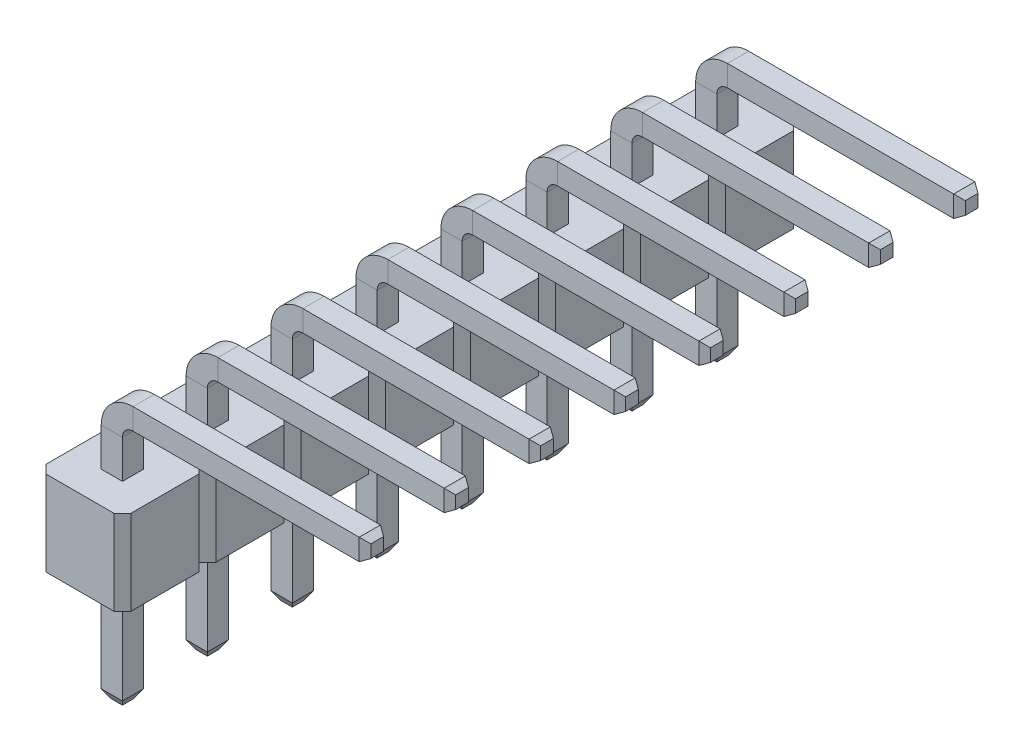
SolidWorks part; units mm, degrees
ref_plane "Front Plane" through (0, 0, 0) normal (0, 0, 1) x (1, 0, 0)
ref_plane "Top Plane" through (0, 0, 0) normal (0, 1, 0) x (1, 0, 0)
ref_plane "Right Plane" through (0, 0, 0) normal (1, 0, 0) x (0, 0, -1)
sketch "Sketch1" plane through (0, 0, 0) normal (0, 1, 0) x (1, 0, 0)
  line L0 (1.016, 1.27) -> (1.27, 1.016)
  line L1 (-1.016, -1.27) -> (1.016, -1.27)
  line L2 (-1.27, -1.016) -> (-1.27, 1.016)
  line L3 (-1.016, 1.27) -> (1.016, 1.27)
  line L4 (1.27, -1.016) -> (1.27, 1.016)
  line L5 (-1.27, -1.27) -> (1.27, 1.27) construction
  line L6 (-1.27, 1.27) -> (1.27, -1.27) construction
  line L7 (1.016, -1.27) -> (1.27, -1.016)
  line L8 (-1.27, -1.016) -> (-1.016, -1.27)
  line L9 (-1.27, 1.016) -> (-1.016, 1.27)
  point P0 (0, 0)
  dimension "D1" = 2.54
  dimension "D2" = 2.54
extrude "Boss-Extrude1" add sketch "Sketch1" along normal blind 2.54
sketch "Sketch2" plane through (0, 0, 0) normal (0, 0, 1) x (1, 0, 0)
  line L0 (0, 0) -> (0, -3.4036)
  line L1 (0, 0) -> (0, 3.683)
  line L2 (0.635, 4.318) -> (7.62, 4.318)
  line L3 (-1.016, 2.54) -> (1.016, 2.54) construction
  arc A0 (0, 3.683) -> (0.635, 4.318) centre (0.635, 3.683) cw
  point P9 (0, 4.318)
  dimension "D4" = 0.635
  dimension "D1" = 1.778
  dimension "D2" = 7.62
  dimension "D3" = 3.4036
ref_plane "Plane1" through (0, -3.4036, 0) normal (0, -1, 0) x (-1, 0, 0)
sketch "Sketch3" plane through (0, -3.4036, 0) normal (0, -1, 0) x (-1, 0, 0)
  line L1 (0.3175, 0.3175) -> (-0.3175, 0.3175)
  line L2 (0.3175, 0.3175) -> (0.3175, -0.3175)
  line L3 (0.3175, -0.3175) -> (-0.3175, -0.3175)
  line L4 (-0.3175, 0.3175) -> (-0.3175, -0.3175)
  line L5 (0.3175, 0.3175) -> (-0.3175, -0.3175) construction
  line L6 (0.3175, -0.3175) -> (-0.3175, 0.3175) construction
  point P0 (0, 0)
  dimension "D1" = 0.635
  dimension "D2" = 0.635
sweep "Sweep1" add profiles "Sketch3" path "Sketch2"
chamfer "Chamfer1" distance 0.254 angle 30 4 edges at (0, -3.4036, -0.3175) (-0.3175, -3.4036, 0) (0, -3.4036, 0.3175) (0.3175, -3.4036, 0) first distance on face at (0, -1.7018, -0.3175) first distance on face at (-0.3175, -1.7018, 0) first distance on face at (0, -1.7018, 0.3175) first distance on face at (0.3175, -1.7018, 0)
chamfer "Chamfer2" distance 0.127 angle 60 4 edges at (7.62, 4.318, 0.3175) (7.62, 4.6355, 0) (7.62, 4.318, -0.3175) (7.62, 4.0005, 0) first distance on face at (7.62, 4.318, 0)
pattern_linear "LPattern1" count 8 spacing 2.54 along (0, 0, 1) of "Boss-Extrude1", "Chamfer1", "Chamfer2", "Sweep1"
ref_plane "Plane2" through (0, 0, 8.89) normal (0, 0, 1) x (1, 0, 0)
